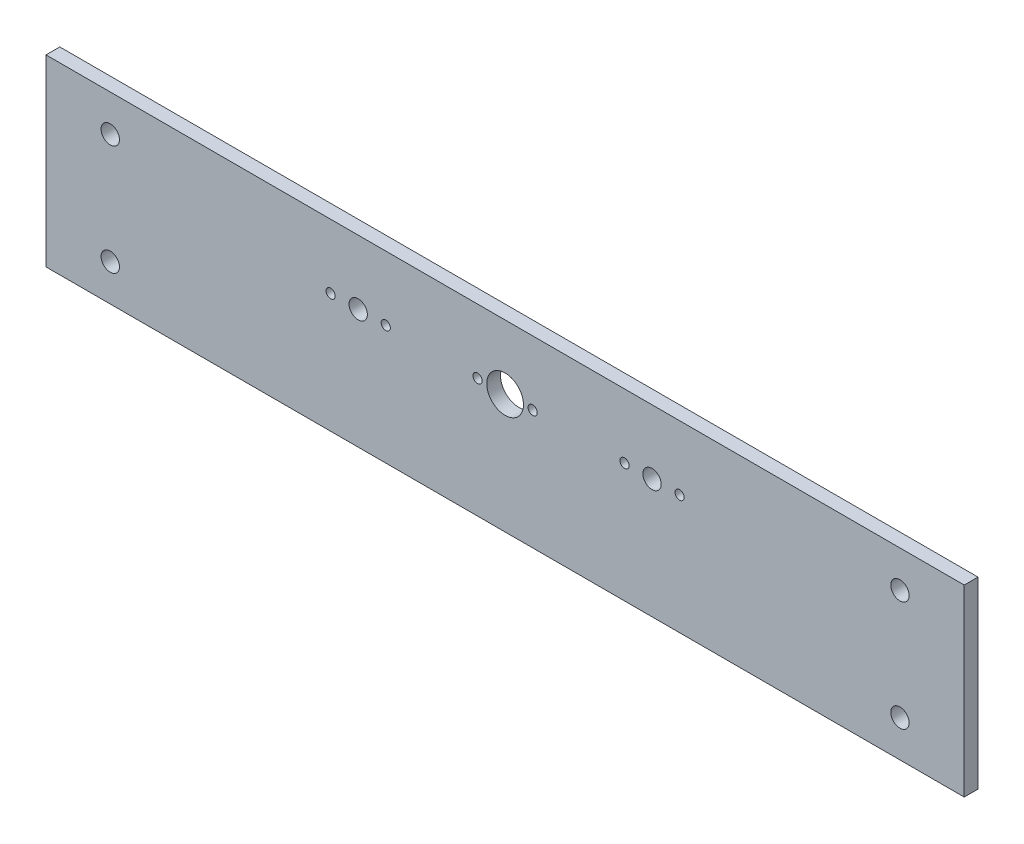
SolidWorks part; units mm, degrees
ref_plane "Front Plane" through (0, 0, 0) normal (0, 0, 1) x (1, 0, 0)
ref_plane "Top Plane" through (0, 0, 0) normal (0, 1, 0) x (1, 0, 0)
ref_plane "Right Plane" through (0, 0, 0) normal (1, 0, 0) x (0, 0, -1)
sketch "Sketch2" plane through (0, 0, 0) normal (0, 0, 1) x (1, 0, 0)
  line L1 (0, 100) -> (500, 100)
  line L2 (0, 100) -> (0, 0)
  line L3 (0, 0) -> (500, 0)
  line L4 (500, 100) -> (500, 0)
  dimension "D1" = 100
  dimension "D2" = 500
extrude "Boss-Extrude1" add sketch "Sketch2" along normal blind 7.5
sketch "Sketch9" plane through (0, 0, 7.5) normal (0, 0, 1) x (1, 0, 0)
  circle A0 centre (170, 65) radius 5
  circle A1 centre (185, 65) radius 2.5
  circle A2 centre (155, 65) radius 2.5
  circle A3 centre (330, 65) radius 5
  circle A4 centre (345, 65) radius 2.5
  circle A5 centre (315, 65) radius 2.5
  circle A6 centre (250, 65) radius 10
  circle A7 centre (265, 65) radius 2.5
  circle A8 centre (235, 65) radius 2.5
extrude "Cut-Extrude3" cut sketch "Sketch9" against normal through all
sketch "Sketch11" plane through (0, 0, 7.5) normal (0, 0, 1) x (1, 0, 0)
  circle A0 centre (35, 80) radius 5
  circle A1 centre (35, 20) radius 5
  circle A2 centre (465, 20) radius 5
  circle A3 centre (465, 80) radius 5
  dimension "D1" = 2
  dimension "D2" = 60
extrude "Cut-Extrude4" cut sketch "Sketch11" against normal through all
